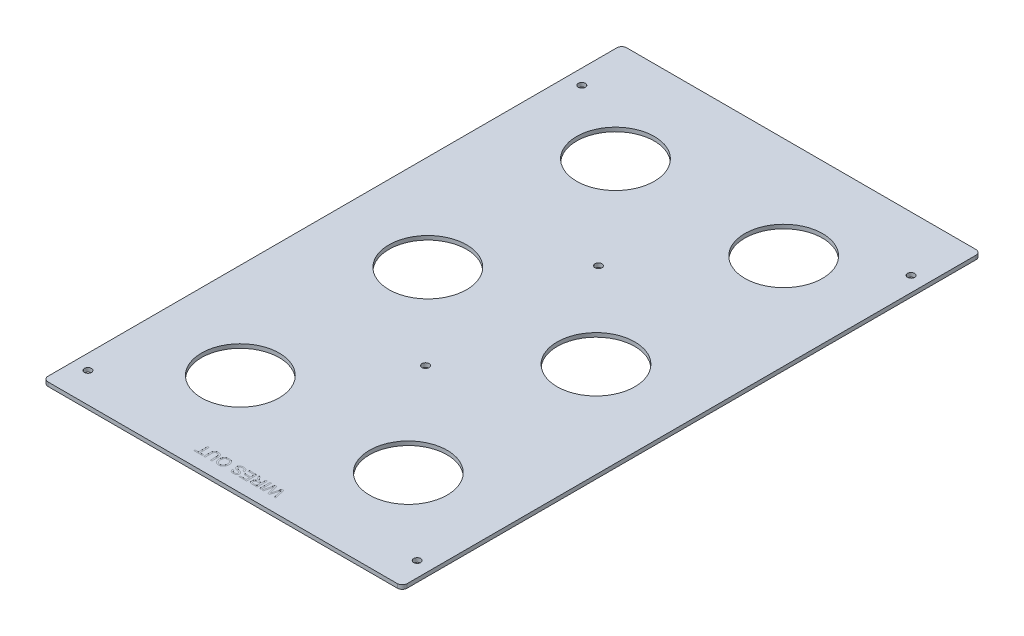
SolidWorks part; units mm, degrees
ref_plane "Front" through (0, 0, 0) normal (0, 0, 1) x (1, 0, 0)
ref_plane "Top" through (0, 0, 0) normal (0, 1, 0) x (1, 0, 0)
ref_plane "Right" through (0, 0, 0) normal (1, 0, 0) x (0, 0, -1)
sketch "Sketch1" plane through (0, 0, 0) normal (0, 1, 0) x (1, 0, 0)
  line L0 (-78.1178, -119.38) -> (-78.2448, -119.38) construction
  line L1 (-111.125, 184.15) -> (111.125, 184.15)
  line L2 (-114.3, 180.975) -> (-114.3, -180.975)
  line L3 (-111.125, -184.15) -> (111.125, -184.15)
  line L4 (114.3, 180.975) -> (114.3, -180.975)
  line L5 (-114.3, 184.15) -> (114.3, -184.15) construction
  line L6 (-114.3, -184.15) -> (114.3, 184.15) construction
  circle A0 centre (53.5178, -119.5086) radius 24.727
  circle A1 centre (53.5178, -0.0643) radius 24.727
  circle A2 centre (-53.5178, -119.38) radius 24.727
  circle A3 centre (-53.5178, -0.0643) radius 24.727
  circle A4 centre (-53.5178, 119.38) radius 24.727
  circle A5 centre (53.5178, 119.38) radius 24.727
  arc A6 (-64.6679, -97.452) -> (-49.567, -143.6607) centre (-53.5178, -119.38) ccw construction
  arc A7 (-64.6679, -97.452) -> (-42.3677, -141.308) centre (-53.5178, -119.38) ccw construction
  arc A8 (114.3, 180.975) -> (111.125, 184.15) centre (111.125, 180.975) ccw
  arc A9 (-114.3, 180.975) -> (-111.125, 184.15) centre (-111.125, 180.975) cw
  arc A10 (-114.3, -180.975) -> (-111.125, -184.15) centre (-111.125, -180.975) ccw
  arc A11 (111.125, -184.15) -> (114.3, -180.975) centre (111.125, -180.975) ccw
  point P0 (0, 0)
  dimension "D3" = 0.127
  dimension "D4" = 3.175
  dimension "D1" = 228.6
  dimension "D2" = 368.3
extrude "Boss-Extrude1" add sketch "Sketch1" along normal blind 2.54
sketch "Sketch2" plane through (0, 2.54, 0) normal (0, 1, 0) x (1, 0, 0)
  line L0 (0, -184.15) -> (0, -168.91) construction
  line L1 (-111.125, -184.15) -> (111.125, -184.15) construction
  line L2 (25.4, -168.91) -> (-25.4, -168.91) construction
  text T0 "WIRES OUT" font "Arial" height in points 26
  point P7 (0, -168.91)
  dimension "D1" = 15.24
  dimension "D2" = 50.8
extrude "Cut-Extrude2" cut sketch "Sketch2" against normal blind 0.0254
sketch "Sketch3" plane through (0, 2.54, 0) normal (0, 1, 0) x (1, 0, 0)
  line L0 (53.5178, -144.2356) -> (53.5178, -184.15) construction
  line L1 (-111.125, -184.15) -> (111.125, -184.15) construction
  line L2 (53.5178, 144.107) -> (53.5178, 184.15) construction
  line L3 (111.125, 184.15) -> (-111.125, 184.15) construction
  circle A0 centre (53.5178, -119.5086) radius 24.727 construction
  circle A1 centre (53.5178, 119.38) radius 24.727 construction
hole_wizard "#8 Clearance Hole1" positions "Sketch4" profile "Sketch6" hole size "#8" standard "ANSI Inch" end condition through all
sketch "Sketch4" plane through (0, 0, 0) normal (0, -1, 0) x (-1, 0, 0)
  point P0 (104.775, -165.1)
  point P3 (-104.775, -165.1)
  point P6 (-104.775, 149.225)
  point P9 (104.775, 149.225)
  point P13 (0, -55.0333)
  point P16 (0, 55.0333)
sketch "Sketch6" plane through (-104.775, 0, 165.1) normal (1, 0, 0) x (0, 0, -1)
  line L0 (0, 0) -> (0, 2.54)
  line L1 (0, 2.54) -> (2.2479, 2.54)
  line L2 (2.2479, 2.54) -> (2.2479, 0)
  line L5 (2.2479, 0) -> (0, 0)
  line L11 (0, -6.35) -> (0, 107.95) construction
  dimension "Thru Hole Dia." = 4.4958
  dimension "Thru Hole Depth" = 2.54
